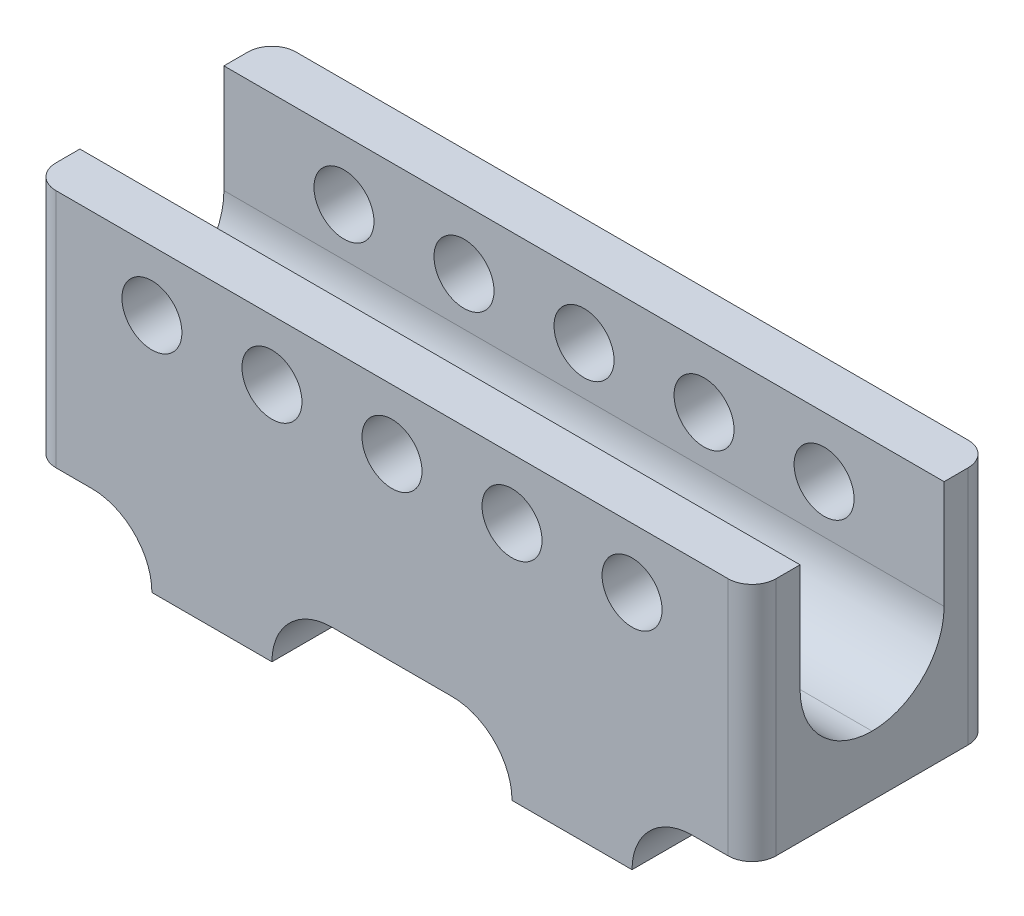
SolidWorks part; units mm, degrees
ref_plane "Front Plane" through (0, 0, 0) normal (0, 0, 1) x (1, 0, 0)
ref_plane "Top Plane" through (0, 0, 0) normal (0, 1, 0) x (1, 0, 0)
ref_plane "Right Plane" through (0, 0, 0) normal (1, 0, 0) x (0, 0, -1)
sketch "Sketch1" plane through (0, 0, 0) normal (0, 1, 0) x (1, 0, 0)
  line L1 (-38.1, 12.7) -> (38.1, 12.7)
  line L2 (-38.1, 12.7) -> (-38.1, -12.7)
  line L3 (-38.1, -12.7) -> (38.1, -12.7)
  line L4 (38.1, 12.7) -> (38.1, -12.7)
  point P4 (86.7912, -56.4433)
  point P5 (0, 12.7)
  point P7 (38.1, 0)
  dimension "D1" = 76.2
  dimension "D2" = 25.4
extrude "Boss-Extrude1" add sketch "Sketch1" along normal blind 31.75
sketch "Sketch2" plane through (38.1, 0, 0) normal (1, 0, 0) x (0, 0, -1)
  line L0 (-12.7, 31.75) -> (12.7, 31.75) construction
  line L1 (-7.62, 31.75) -> (7.62, 31.75)
  line L2 (-7.62, 31.75) -> (-7.62, 12.7)
  line L3 (-7.62, 12.7) -> (7.62, 12.7)
  line L4 (7.62, 31.75) -> (7.62, 12.7)
  line L5 (0, 55) -> (0, -55) construction
  line L6 (-12.7, 0) -> (12.7, 0) construction
  point P6 (0, 12.7)
  dimension "D1" = 12.7
  dimension "D2" = 15.24
extrude "Cut-Extrude1" cut sketch "Sketch2" against normal up to next
sketch "Sketch3" plane through (0, 0, 12.7) normal (0, 0, 1) x (1, 0, 0)
  line L0 (-38.1, 31.75) -> (38.1, 31.75) construction
  line L1 (-38.1, 31.75) -> (-38.1, 0) construction
  circle A0 centre (-25.4, 25.4) radius 3.175
  dimension "D1" = 6.35
  dimension "D2" = 6.35
  dimension "D3" = 12.7
extrude "Cut-Extrude2" cut sketch "Sketch3" against normal through all
pattern_linear "LPattern1" count 5 spacing 12.7 along (1, 0, 0) of "Cut-Extrude2"
hole_wizard "CBORE for #6 Binding Head Machine Screw1" positions "Sketch4" profile "Sketch5" counterbore size "#6" standard "ANSI Inch" end condition up to next
sketch "Sketch4" plane through (0, 12.7, 0) normal (0, 1, 0) x (1, 0, 0)
  line L0 (-19.05, 0) -> (19.05, 0) construction
  point P0 (-19.05, 0)
  point P2 (19.05, 0)
  point P11 (0, 0)
  dimension "D1" = 38.1
sketch "Sketch5" plane through (-19.05, 12.7, 0) normal (1, 0, 0) x (0, 0, 1)
  line L0 (0, 0) -> (0, 12.7)
  line L1 (0, 12.7) -> (1.8986, 12.7)
  line L3 (1.8986, 12.7) -> (1.8987, 2.2098)
  line L4 (1.8987, 2.2098) -> (3.9687, 2.2098)
  line L5 (3.9687, 2.2098) -> (3.9687, 0)
  line L7 (3.9687, 0) -> (0, 0)
  line L11 (0, -6.35) -> (0, 107.95) construction
  dimension "Thru Hole Dia." = 3.7973
  dimension "Thru Hole Depth" = 12.7
  dimension "C'Bore Dia." = 7.9375
  dimension "C'Bore Depth" = 2.2098
fillet "Fillet2" radius 7.62 2 edges at (0, 12.7, -7.62) (0, 12.7, 7.62)
sketch "Sketch7" plane through (0, 0, 12.7) normal (0, 0, 1) x (1, 0, 0)
  line L0 (-38.1, 31.75) -> (-38.1, 0) construction
  line L1 (-38.1, 6.35) -> (-25.4, 6.35)
  line L2 (-38.1, 6.35) -> (-38.1, 0)
  line L3 (-38.1, 0) -> (-25.4, 0)
  line L4 (38.1, 6.35) -> (38.1, 0)
  line L5 (-25.4, 6.35) -> (-25.4, 0)
  line L6 (-12.7, 6.35) -> (-12.7, 0)
  line L7 (12.7, 6.35) -> (12.7, 0)
  line L8 (25.4, 6.35) -> (25.4, 0)
  line L10 (-12.7, 6.35) -> (12.7, 6.35)
  line L11 (-12.7, 0) -> (12.7, 0)
  line L12 (25.4, 6.35) -> (38.1, 6.35)
  line L13 (25.4, 0) -> (38.1, 0)
  line L14 (0, -13.97) -> (0, 13.97) construction
  point P15 (0, 6.35)
  dimension "D1" = 6.35
  dimension "D2" = 25.4
  dimension "D3" = 12.7
  dimension "D4" = 12.7
extrude "Cut-Extrude3" cut sketch "Sketch7" against normal up to next
fillet "Fillet5" radius 6.35 4 edges at (-25.4, 6.35, 0) (-12.7, 6.35, 0) (12.7, 6.35, 0) (25.4, 6.35, 0)
fillet "Fillet6" radius 2.54 4 edges at (-38.1, 19.05, -12.7) (-38.1, 19.05, 12.7) (38.1, 19.05, -12.7) (38.1, 19.05, 12.7)
